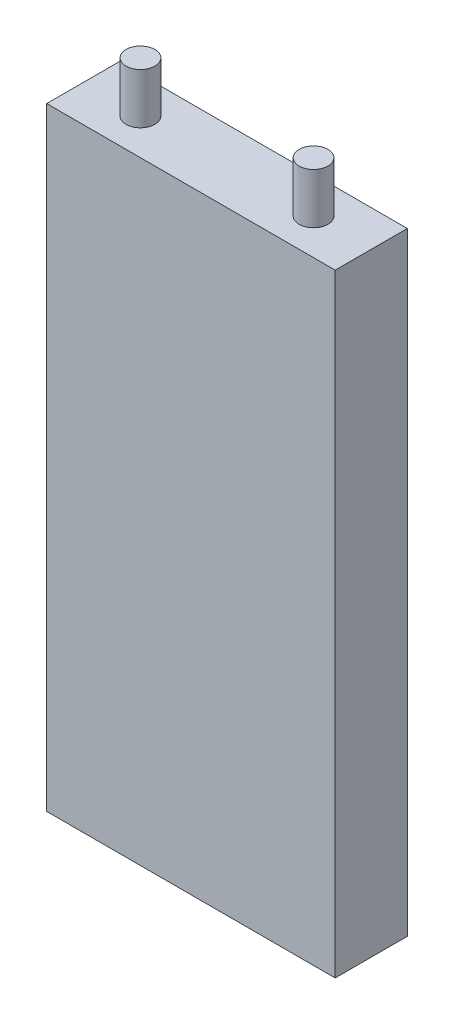
SolidWorks part; units mm, degrees
ref_plane "Front Plane" through (0, 0, 0) normal (0, 0, 1) x (1, 0, 0)
ref_plane "Top Plane" through (0, 0, 0) normal (0, 1, 0) x (1, 0, 0)
ref_plane "Right Plane" through (0, 0, 0) normal (1, 0, 0) x (0, 0, -1)
sketch "Sketch1" plane through (0, 0, 0) normal (0, 1, 0) x (1, 0, 0)
  line L1 (0, -10.671) -> (-21.342, -10.671) construction
  line L7 (-21.342, -10.671) -> (80.258, -10.671)
  line L8 (-21.342, -10.671) -> (-21.342, 14.729)
  line L9 (-21.342, 14.729) -> (80.258, 14.729)
  line L10 (80.258, -10.671) -> (80.258, 14.729)
extrude "Boss-Extrude1" add sketch "Sketch1" along normal blind 215.9 contours L9 L10 L7 L8
sketch "Sketch2" plane through (0, 215.9, 0) normal (0, 1, 0) x (1, 0, 0)
  line L0 (29.458, 14.729) -> (29.458, -10.671) construction
  line L1 (-21.342, 14.729) -> (80.258, 14.729) construction
  line L2 (-21.342, -10.671) -> (80.258, -10.671) construction
  line L3 (29.458, 2.029) -> (15.488, 2.029) construction
  line L4 (29.458, 2.029) -> (-1.022, 2.029) construction
  line L5 (29.458, 2.029) -> (59.938, 2.029) construction
  circle A1 centre (-1.022, 2.029) radius 5.08
  circle A2 centre (59.938, 2.029) radius 5.08
  dimension "D1" = 10.16
  dimension "D2" = 10.16
extrude "Boss-Extrude2" add sketch "Sketch2" along normal blind 17.78
